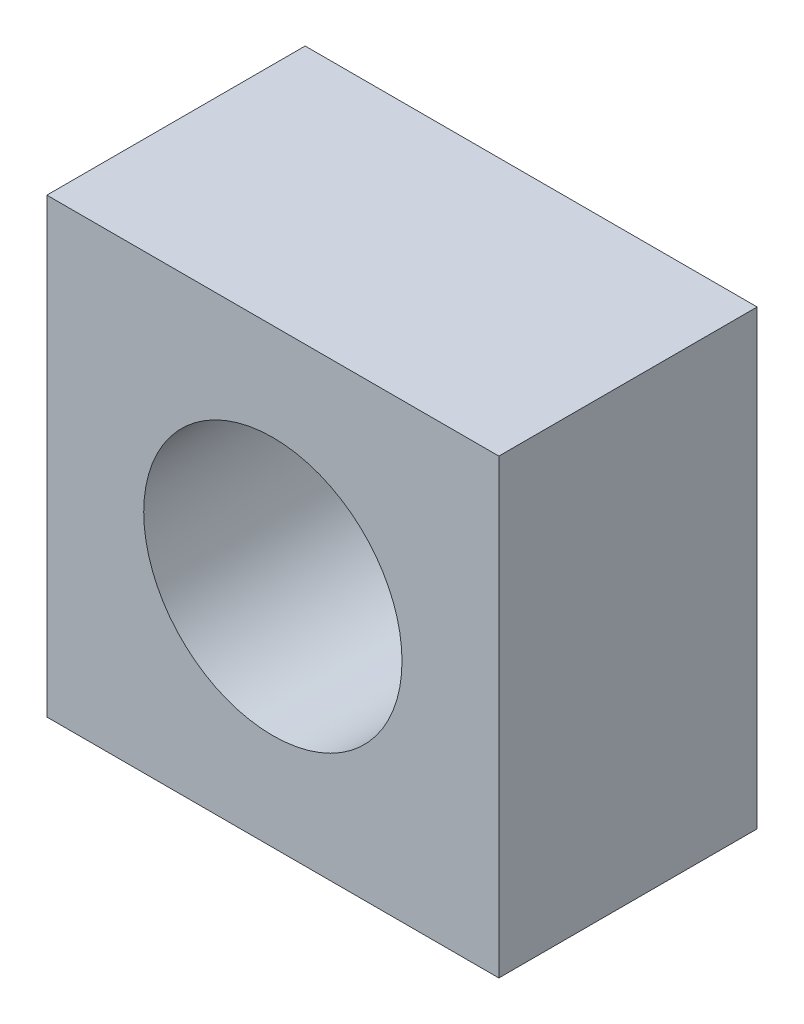
SolidWorks part; units mm, degrees
ref_plane "Front Plane" through (0, 0, 0) normal (0, 0, 1) x (1, 0, 0)
ref_plane "Top Plane" through (0, 0, 0) normal (0, 1, 0) x (1, 0, 0)
ref_plane "Right Plane" through (0, 0, 0) normal (1, 0, 0) x (0, 0, -1)
sketch "Sketch2" plane through (0, 0, 0) normal (0, 0, 1) x (1, 0, 0)
  line L1 (-17.5, -17.5) -> (17.5, -17.5)
  line L2 (-17.5, -17.5) -> (-17.5, 17.5)
  line L3 (-17.5, 17.5) -> (17.5, 17.5)
  line L4 (17.5, -17.5) -> (17.5, 17.5)
  line L5 (-17.5, -17.5) -> (17.5, 17.5) construction
  line L6 (-17.5, 17.5) -> (17.5, -17.5) construction
  circle A0 centre (0, 0) radius 10
  dimension "D1" = 20
  dimension "D2" = 35
  dimension "D3" = 35
extrude "Boss-Extrude1" add sketch "Sketch2" along normal blind 20
sketch "Sketch3" plane through (0, 0, 0) normal (0, 0, 1) x (1, 0, 0)
  line L0 (-7.5, 17.5) -> (-7.5, -2.5)
  line L1 (17.5, 17.5) -> (-17.5, 17.5) construction
  line L2 (7.5, 17.5) -> (7.5, -2.5)
  line L3 (0, 0) -> (0, 17.5) construction
  arc A0 (7.5, -2.5) -> (-7.5, -2.5) centre (0, -2.5) cw
  dimension "D1" = 20
  dimension "D2" = 15
